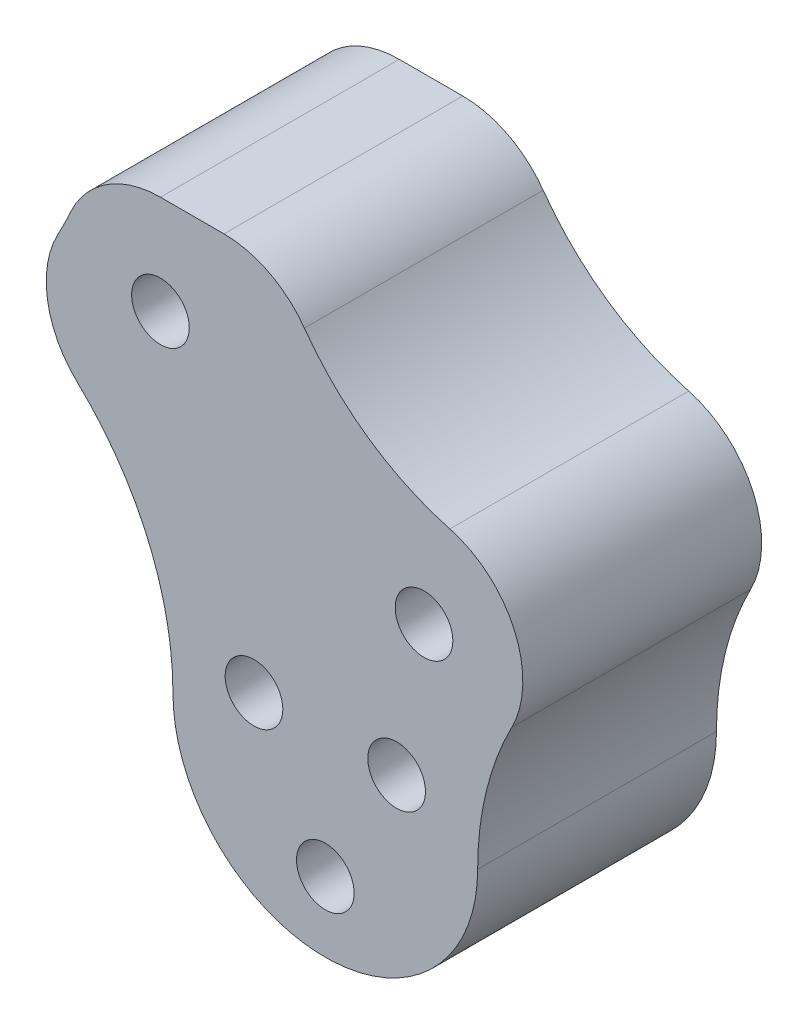
SolidWorks part; units mm, degrees
ref_plane "前视" through (0, 0, 0) normal (0, 0, 1) x (1, 0, 0)
ref_plane "上视" through (0, 0, 0) normal (0, 1, 0) x (1, 0, 0)
ref_plane "右视" through (0, 0, 0) normal (1, 0, 0) x (0, 0, -1)
sketch "草图1" plane through (0, 0, 0) normal (0, 0, 1) x (-1, 0, 0)
  line L0 (-50.2482, -8.7376) -> (15.7518, -8.7376)
  line L1 (15.7518, 19.2624) -> (5.2518, 19.2624)
  line L2 (-37.4053, 24.4466) -> (-45.3555, 16.7788)
  line L3 (-19.7585, 12.0484) -> (-8.3095, 12.0484)
  arc A0 (15.7518, -8.7376) -> (15.7518, 19.2624) centre (15.7518, 5.2624) ccw
  arc A1 (-13.2482, 37.7624) -> (5.2518, 19.2624) centre (5.2518, 37.7624) ccw
  arc A2 (-13.2482, 37.7624) -> (-31.7482, 37.7624) centre (-22.4982, 37.7624) ccw
  arc A3 (-50.2482, 19.2624) -> (-31.7482, 37.7624) centre (-50.2482, 37.7624) ccw
  arc A4 (-50.2482, 19.2624) -> (-50.2482, -8.7376) centre (-50.2482, 5.2624) ccw
  circle A5 centre (-34.2482, 5.2624) radius 16
  circle A6 centre (15.7518, 5.2624) radius 25
  circle A7 centre (15.7518, 5.2624) radius 4.25
  circle A8 centre (-34.2482, 5.2624) radius 2
  dimension "D1" = 32
  dimension "D2" = 50
extrude "凸台-拉伸2" add sketch "草图1" along normal blind 14.5 contours A6 L1 A1 A2 A3 A5 region at (20.9464, -28.3885, 0)
fillet "圆角2" radius 6 4 edges at (3.354, -21.3859, 7.25) (45.3555, -16.7788, 7.25) (8.3095, -12.0484, 7.25) (19.7585, -12.0484, 7.25)
sketch "草图2" plane through (0, 0, 14.5) normal (0, 0, 1) x (1, 0, 0)
  circle A0 centre (22.4982, -37.7624) radius 5 construction
  circle A1 centre (22.4982, -42.7624) radius 1.75
  circle A2 centre (18.168, -35.2624) radius 1.75
  circle A3 centre (26.8283, -35.2624) radius 1.75
  circle A4 centre (28.4922, -26.4961) radius 1.75
  circle A5 centre (12.4885, -18.0484) radius 1.75
  point P12 (22.4982, -37.7624)
  dimension "D1" = 10
  dimension "D2" = 3.5
  dimension "D4" = 3.5
  dimension "D5" = 3.5
  dimension "D3" = 3
extrude "切除-拉伸1" cut sketch "草图2" against normal up to next
